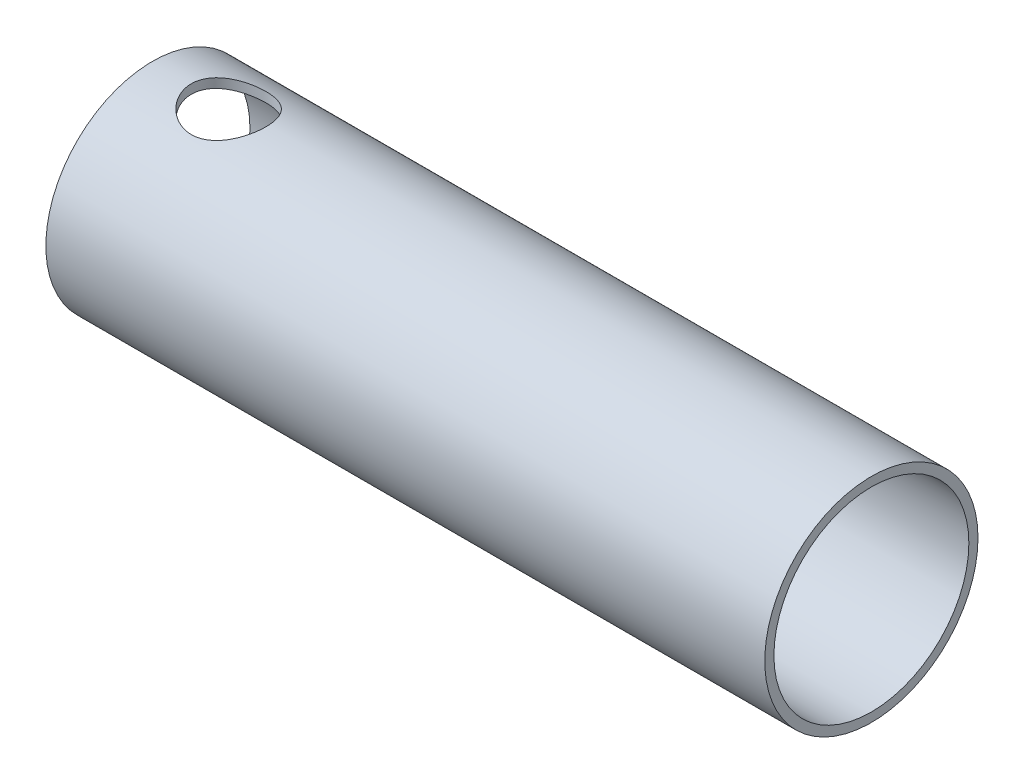
SolidWorks part; units mm, degrees
ref_plane "Front Plane" through (0, 0, 0) normal (0, 0, 1) x (1, 0, 0)
ref_plane "Top Plane" through (0, 0, 0) normal (0, 1, 0) x (1, 0, 0)
ref_plane "Right Plane" through (0, 0, 0) normal (1, 0, 0) x (0, 0, -1)
sketch "Sketch3" plane through (0, 0, 0) normal (1, 0, 0) x (0, 0, -1)
  circle A0 centre (0, 0) radius 32
  circle A1 centre (0, 0) radius 35
  dimension "D1" = 64
  dimension "D2" = 70
extrude "Boss-Extrude1" add sketch "Sketch3" along normal blind 236
sketch "Sketch4" plane through (0, 0, 0) normal (0, 1, 0) x (1, 0, 0)
  circle A0 centre (25, 0) radius 12.25
  dimension "D2" = 24.5
  dimension "D1" = 25
extrude "Cut-Extrude1" cut sketch "Sketch4" against normal through all both and the other way through all
